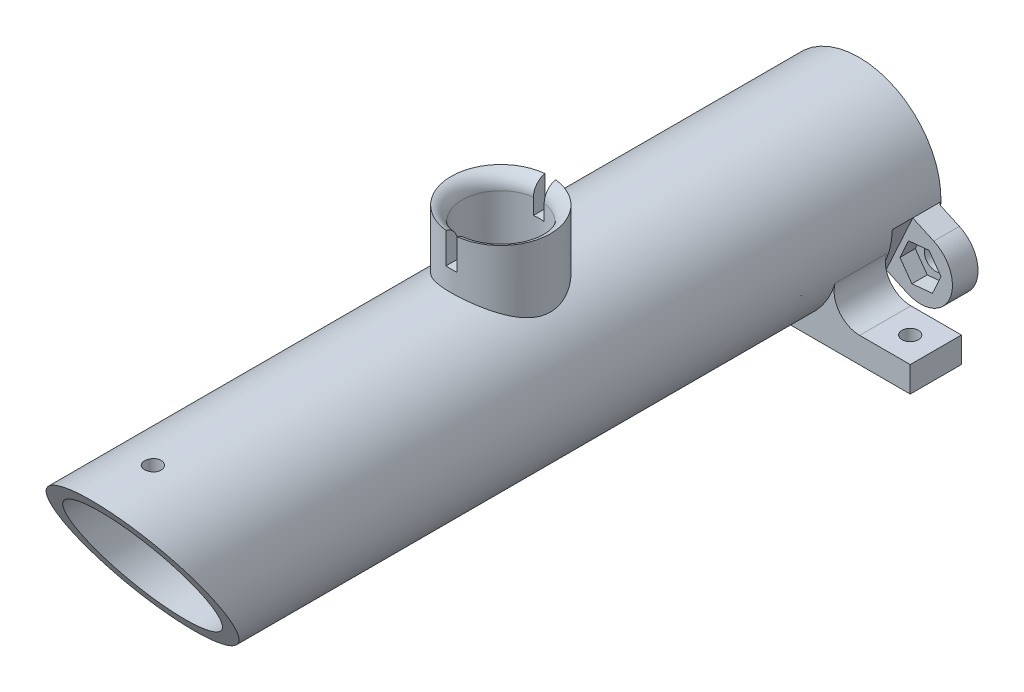
SolidWorks part; units mm, degrees
ref_plane "Front Plane" through (0, 0, 0) normal (0, 0, 1) x (1, 0, 0)
ref_plane "Top Plane" through (0, 0, 0) normal (0, 1, 0) x (1, 0, 0)
ref_plane "Right Plane" through (0, 0, 0) normal (1, 0, 0) x (0, 0, -1)
sketch "Sketch4" plane through (0, 0, 0) normal (0, 0, 1) x (1, 0, 0)
  circle A0 centre (0, 0) radius 16
  circle A1 centre (0, 0) radius 13.25
  dimension "D1" = 26.5
  dimension "D2" = 32
extrude "Boss-Extrude3" add sketch "Sketch4" along normal blind 150
sketch "Sketch5" plane through (0, 0, 150) normal (0, 0, 1) x (1, 0, 0)
  circle A0 centre (0, 0) radius 16 construction
  point P0 (0, 16)
  point P1 (16, 0)
  point P4 (-16, 0)
  point P5 (0, -16)
ref_plane "Plane1" through (0, 16, 150) normal (0, 1, 0) x (1, 0, 0)
sketch "Sketch6" plane through (0, 16, 150) normal (0, 1, 0) x (1, 0, 0)
  line L0 (-16, 0) -> (16, 0) construction
  circle A0 centre (0, 80) radius 7.5
  circle A1 centre (0, 80) radius 9.7
  dimension "D1" = 15
  dimension "D2" = 2.2
  dimension "D3" = 80
extrude "Boss-Extrude4" add sketch "Sketch6" along normal blind 10 and the other way blind 4
sketch "Sketch7" plane through (0, 26, 0) normal (0, 1, 0) x (1, 0, 0)
  circle A0 centre (0, -70) radius 7.5
  circle A1 centre (0, -70) radius 7.5 construction
extrude "Cut-Extrude1" cut sketch "Sketch7" against normal blind 20
sketch "Sketch8" plane through (0, 0, 150) normal (0, 0, 1) x (1, 0, 0)
  circle A0 centre (0, 0) radius 13.25
extrude "Cut-Extrude2" cut sketch "Sketch8" against normal up to surface (150 mm away) up to face at (16, 0, 0)
sketch "Sketch11" plane through (0, 16, 150) normal (0, 1, 0) x (1, 0, 0)
  line L0 (-16, 0) -> (16, 0) construction
  circle A0 centre (0, 12) radius 1.6
  dimension "D1" = 3.2
  dimension "D2" = 12
extrude "Cut-Extrude5" cut sketch "Sketch11" against normal blind 13
sketch "Sketch13" plane through (0, 0, 0) normal (0, 0, -1) x (-1, 0, 0)
  point P0 (16, 0)
ref_plane "Plane4" through (-16, 0, 0) normal (-1, 0, 0) x (0, 0, 1)
sketch "Sketch14" plane through (-16, 0, 0) normal (-1, 0, 0) x (0, 0, 1)
  line L5 (150, 16) -> (130, -16)
  line L6 (0, -16) -> (150, -16) construction
  line L7 (130, -16) -> (150, -16)
  line L8 (150, -16) -> (150, 16)
  dimension "D1" = 20
extrude "Cut-Extrude7" cut sketch "Sketch14" against normal blind 42.3
ref_plane "Plane5" through (0, -16, 150) normal (0, -1, 0) x (-1, 0, 0)
sketch "Sketch15" plane through (0, -16, 150) normal (0, -1, 0) x (-1, 0, 0)
  line L0 (0, 150) -> (0, 0) construction
  line L1 (-30, 130) -> (30, 130)
  line L2 (-30, 130) -> (-30, 140)
  line L3 (-30, 140) -> (30, 140)
  line L4 (30, 130) -> (30, 140)
  line L5 (-30, 130) -> (30, 140) construction
  line L6 (-30, 140) -> (30, 130) construction
  line L7 (16, 150) -> (-16, 150) construction
  circle A0 centre (-25, 135) radius 1.6
  circle A1 centre (25, 135) radius 1.6
  point P0 (0, 135)
  point P15 (0, 135)
  dimension "D4" = 3.2
  dimension "D5" = 3.2
  dimension "D7" = 5
  dimension "D8" = 25
  dimension "D9" = 5
  dimension "D1" = 60
  dimension "D2" = 15
  dimension "D3" = 10
  dimension "D6" = 50
extrude "Boss-Extrude5" add sketch "Sketch15" against normal blind 5
sketch "Sketch16" plane through (0, 0, 0) normal (0, 0, -1) x (-1, 0, 0)
  circle A0 centre (0, 0) radius 13.25
extrude "Cut-Extrude8" cut sketch "Sketch16" against normal up to vertex (150 mm away) up to point (0, 16, 150)
fillet "Fillet2" radius 3 1 edges at (-7.5, 26, 70)
fillet "Fillet3" radius 5 2 edges at (-11.619, -11, 15) (11.619, -11, 15)
sketch "Sketch20" plane through (0, 16, 150) normal (0, 1, 0) x (1, 0, 0)
  line L1 (-1.05, 89.7) -> (1.05, 89.7)
  line L2 (-1.05, 89.7) -> (-1.05, 86.7)
  line L3 (-1.05, 86.7) -> (1.05, 86.7)
  line L4 (1.05, 89.7) -> (1.05, 86.7)
  line L5 (-1.05, 73.3) -> (1.05, 73.3)
  line L6 (-1.05, 73.3) -> (-1.05, 70.3)
  line L7 (-1.05, 70.3) -> (1.05, 70.3)
  line L8 (1.05, 73.3) -> (1.05, 70.3)
  circle A2 centre (0, 80) radius 9.7 construction
  circle A3 centre (0, 80) radius 4.7474
  circle A4 centre (0, 80) radius 7.5 construction
  point P14 (0, 73.3)
  point P15 (0, 86.7)
  dimension "D1" = 2.1
  dimension "D2" = 3
extrude "Cut-Extrude10" cut sketch "Sketch20" along normal blind 6 from offset 4
sketch "Sketch21" plane through (0, 0, 0) normal (0, 0, -1) x (-1, 0, 0)
  line L0 (17.5, 8) -> (-17.5, 8)
  line L1 (17.5, 8) -> (17.5, -8)
  line L2 (-17.5, 8) -> (-17.5, -8)
  line L3 (17.5, -8) -> (-17.5, -8)
  line L4 (17.5, 8) -> (-17.5, -8) construction
  line L5 (-17.5, 8) -> (17.5, -8) construction
  line L6 (-17.6, -16) -> (17.6, -16) construction
  line L7 (-17.5, -8) -> (0, 0) construction
  line L8 (-20.0985, -2.3158) -> (-2.5985, 5.6842)
  line L9 (-14.9015, -13.6842) -> (2.5985, -5.6842)
  line L10 (17.5, -8) -> (0, 0) construction
  line L11 (14.9015, -13.6842) -> (-2.5985, -5.6842)
  line L12 (20.0985, -2.3158) -> (2.5985, 5.6842)
  circle A0 centre (-17.5, -8) radius 2.25
  circle A1 centre (17.5, -8) radius 2.25
  arc A2 (-20.0985, -2.3158) -> (-14.9015, -13.6842) centre (-17.5, -8) ccw
  arc A3 (2.5985, -5.6842) -> (-2.5985, 5.6842) centre (0, 0) ccw
  arc A4 (14.9015, -13.6842) -> (20.0985, -2.3158) centre (17.5, -8) ccw
  arc A5 (2.5985, 5.6842) -> (-2.5985, -5.6842) centre (0, 0) ccw
  circle A6 centre (0, 0) radius 13.25
  point P1 (0, 0)
  point P10 (-8.75, -4)
  point P16 (8.75, -4)
  circle M12 centre (0, 0) radius 16
  dimension "D3" = 4.5
  dimension "D4" = 4
  dimension "D5" = 4
  dimension "D1" = 16
  dimension "D2" = 35
extrude "Boss-Extrude6" add sketch "Sketch21" against normal blind 5 from offset 0.5 contours L8 A2 L9 L3 A0 L2 M12 | A0 L3 L8 L2 M12 | L11 A4 L12 L1 A1 L3 M12 | A1 L1 L12 L3 M12 offset against normal yes
fillet "Fillet4" radius 0.5 2 edges at (14.5516, -6.6522, 0.5) (-14.5516, -6.6522, 0.5)
sketch "Sketch22" plane through (0, 0, 5.5) normal (0, 0, 1) x (1, 0, 0)
  line L0 (15.994, -0.4394) -> (10.797, -11.8079)
  line L1 (15.994, -0.4394) -> (17.3582, -1.0631)
  line L2 (10.797, -11.8079) -> (12.1612, -12.4315)
  line L3 (17.3582, -1.0631) -> (12.1612, -12.4315)
  line L4 (-15.994, -0.4394) -> (-10.797, -11.8079)
  line L5 (-15.994, -0.4394) -> (-17.3582, -1.0631)
  line L6 (-10.797, -11.8079) -> (-12.1612, -12.4315)
  line L7 (-17.3582, -1.0631) -> (-12.1612, -12.4315)
  dimension "D1" = 1.5
extrude "Cut-Extrude11" cut sketch "Sketch22" along normal blind 4
sketch "Sketch23" plane through (0, 0, 5.5) normal (0, 0, 1) x (1, 0, 0)
  line L0 (-10.797, -11.8079) -> (-15.994, -0.4394) construction
  line L1 (-19.127, -4.441) -> (-21.3956, -7.6295)
  line L2 (-21.3956, -7.6295) -> (-19.7687, -11.1885)
  line L3 (-19.7687, -11.1885) -> (-15.873, -11.559)
  line L4 (-15.873, -11.559) -> (-13.6044, -8.3705)
  line L5 (-13.6044, -8.3705) -> (-15.2313, -4.8115)
  line L6 (-15.2313, -4.8115) -> (-19.127, -4.441)
  line L7 (19.175, -4.3358) -> (15.1643, -4.7173)
  line L8 (15.1643, -4.7173) -> (13.4892, -8.3814)
  line L9 (13.4892, -8.3814) -> (15.825, -11.6642)
  line L10 (15.825, -11.6642) -> (19.8357, -11.2827)
  line L11 (19.8357, -11.2827) -> (21.5108, -7.6186)
  line L12 (21.5108, -7.6186) -> (19.175, -4.3358)
  line L13 (15.994, -0.4394) -> (10.797, -11.8079) construction
  circle A0 centre (-17.5, -8) radius 3.3889 construction
  circle A1 centre (17.5, -8) radius 3.4891 construction
extrude "Cut-Extrude12" cut sketch "Sketch23" against normal blind 3
